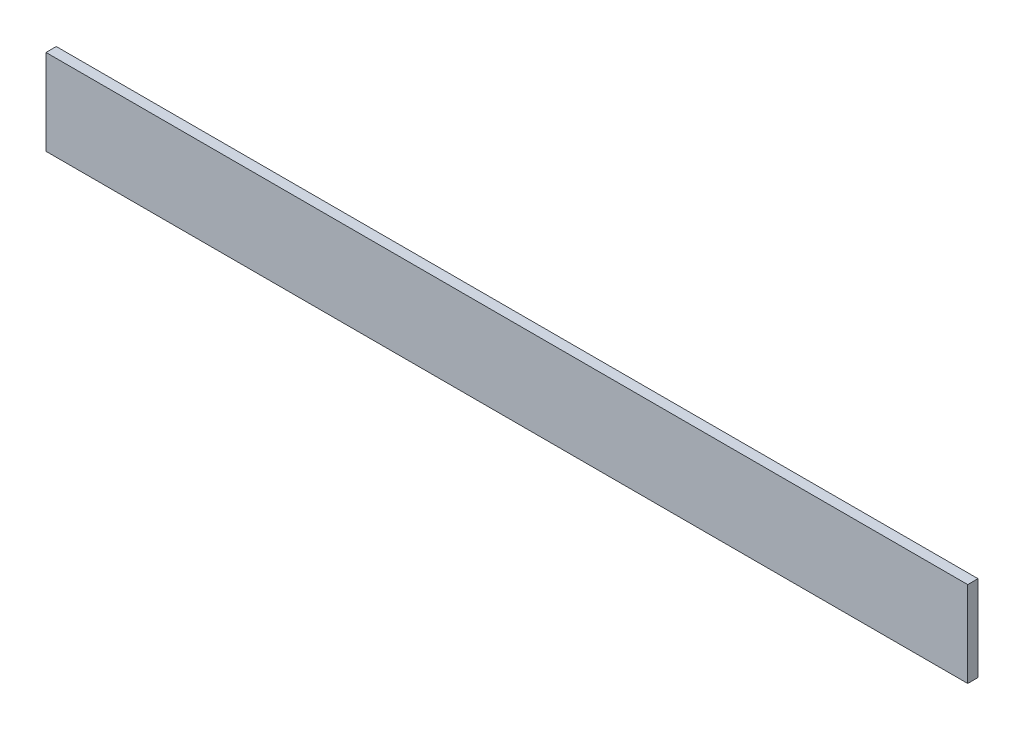
SolidWorks part; units mm, degrees
material "Клен"
ref_plane "Спереди" through (0, 0, 0) normal (0, 0, 1) x (1, 0, 0)
ref_plane "Сверху" through (0, 0, 0) normal (0, 1, 0) x (1, 0, 0)
ref_plane "Справа" through (0, 0, 0) normal (1, 0, 0) x (0, 0, -1)
sketch "Эскиз1" plane through (0, 0, 0) normal (0, 0, 1) x (1, 0, 0)
  line L1 (-173.8303, 0) -> (364.1697, 0)
  line L2 (-173.8303, 0) -> (-173.8303, -50)
  line L3 (-173.8303, -50) -> (364.1697, -50)
  line L4 (364.1697, 0) -> (364.1697, -50)
  dimension "D1" = 538
  dimension "D2" = 50
extrude "Бобышка-Вытянуть1" add sketch "Эскиз1" along normal blind 6
